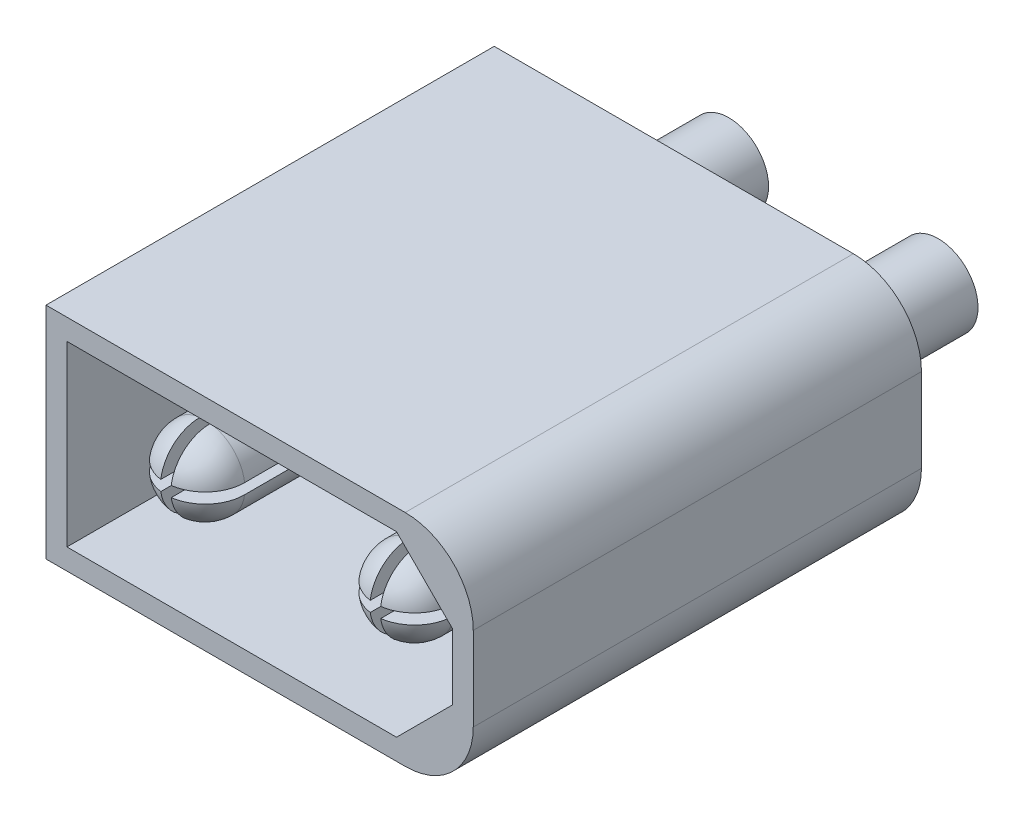
SolidWorks part; units mm, degrees
ref_plane "Front Plane" through (0, 0, 0) normal (0, 0, 1) x (1, 0, 0)
ref_plane "Top Plane" through (0, 0, 0) normal (0, 1, 0) x (1, 0, 0)
ref_plane "Right Plane" through (0, 0, 0) normal (1, 0, 0) x (0, 0, -1)
sketch "Sketch1" plane through (0, 0, 0) normal (0, 0, 1) x (1, 0, 0)
  line L0 (0, 0) -> (10.2, 0) construction
  line L1 (0, -2.625) -> (0, 2.625)
  line L2 (0, 2.625) -> (8.575, 2.625)
  line L4 (10.2, 1) -> (10.2, -1)
  line L5 (5.1, 0) -> (5.1, 1.3562) construction
  line L7 (0, -2.625) -> (8.575, -2.625)
  line L8 (0.5, 2.125) -> (8.3679, 2.125)
  line L9 (8.3679, 2.125) -> (9.7, 0.7929)
  line L10 (9.7, 0.7929) -> (9.7, -0.7929)
  line L11 (8.3679, -2.125) -> (9.7, -0.7929)
  line L12 (0.5, -2.125) -> (8.3679, -2.125)
  line L13 (0.5, -2.125) -> (0.5, 2.125)
  line L14 (8.575, 2.625) -> (10.2, 1) construction
  line L15 (8.575, -2.625) -> (10.2, -1) construction
  circle A0 centre (2.6, 0) radius 0.95
  circle A2 centre (7.6, 0) radius 0.95
  arc A3 (8.575, 2.625) -> (10.2, 1) centre (8.575, 1) cw
  arc A4 (8.575, -2.625) -> (10.2, -1) centre (8.575, -1) ccw
  dimension "D6" = 1.9
  dimension "D1" = 5.25
  dimension "D2" = 10.2
  dimension "D3" = 135
  dimension "D4" = 2.5
  dimension "D7" = 2
  dimension "D5" = 0.5
extrude "Boss-Extrude1" add sketch "Sketch1" along normal blind 10.7 contours L1 L7 A4 L4 A3 L2 L12 L13 L8 L9 L10 L11 region at (0.1147, 0, 0)
extrude "Boss-Extrude5" add sketch "Sketch1<4>" along normal blind 9.5 and the other way blind 3 separate body contours A0 | A2 region at (2.6, 0, 0)
sketch "Sketch1<4>" plane through (0, 0, 0) normal (0, 0, 1) x (1, 0, 0) same geometry as "Sketch1"
ref_plane "Plane1" through (0, 0, 1) normal (0, 0, -1) x (-1, 0, 0)
sketch "Sketch3" plane through (0, 0, 1) normal (0, 0, -1) x (-1, 0, 0)
  line L0 (-0.5, -2.125) -> (-0.5, 2.125) construction
  line L1 (-0.5, -2.125) -> (-8.3679, -2.125) construction
  line L2 (-8.3679, -2.125) -> (-9.7, -0.7929) construction
  line L3 (-9.7, 0.7929) -> (-9.7, -0.7929) construction
  line L4 (-8.3679, 2.125) -> (-9.7, 0.7929) construction
  line L5 (-0.5, 2.125) -> (-8.3679, 2.125) construction
  line L6 (-0.5, -2.125) -> (-0.5, 2.125)
  line L7 (-0.5, -2.125) -> (-8.3679, -2.125)
  line L8 (-8.3679, -2.125) -> (-9.7, -0.7929)
  line L9 (-9.7, 0.7929) -> (-9.7, -0.7929)
  line L10 (-8.3679, 2.125) -> (-9.7, 0.7929)
  line L11 (-0.5, 2.125) -> (-8.3679, 2.125)
extrude "Boss-Extrude3" add sketch "Sketch3" against normal blind 2.5
dome "Dome1" faces to dome 1 distance 0.95 reverse direction no elliptical dome no face at (6.65, 0, 9.5) parameters "D1"=0.95
dome "Dome2" faces to dome 1 distance 0.95 reverse direction no elliptical dome no face at (3.55, 0, 9.5) parameters "D1"=0.95
ref_plane "Plane2" through (0, 0, 6) normal (0, 0, 1) x (1, 0, 0)
sketch "Sketch4" plane through (0, 0, 6) normal (0, 0, 1) x (1, 0, 0)
  line L0 (7.6, 0) -> (2.6, 0) construction
  line L1 (5.1, 0) -> (5.1, -4.8964) construction
  line L2 (7.6, 0) -> (7.6, 0.95) construction
  line L3 (7.475, 0.9417) -> (7.475, 0.125)
  line L4 (7.725, 0.9417) -> (7.725, 0.125)
  line L5 (8.5417, -0.125) -> (7.725, -0.125)
  line L6 (8.5417, 0.125) -> (7.725, 0.125)
  line L7 (7.475, -0.9417) -> (7.475, -0.125)
  line L8 (7.725, -0.9417) -> (7.725, -0.125)
  line L9 (6.6583, 0.125) -> (7.475, 0.125)
  line L10 (6.6583, -0.125) -> (7.475, -0.125)
  line L11 (2.6, 0) -> (2.6, 0.95) construction
  line L12 (3.5417, -0.125) -> (2.725, -0.125)
  line L13 (3.5417, 0.125) -> (2.725, 0.125)
  line L14 (2.475, -0.9417) -> (2.475, -0.125)
  line L15 (2.725, -0.9417) -> (2.725, -0.125)
  line L16 (1.6583, 0.125) -> (2.475, 0.125)
  line L17 (1.6583, -0.125) -> (2.475, -0.125)
  line L18 (2.475, 0.9417) -> (2.475, 0.125)
  line L19 (2.725, 0.9417) -> (2.725, 0.125)
  circle A0 centre (7.6, 0) radius 0.95 construction
  circle A1 centre (2.6, 0) radius 0.95 construction
  arc A2 (7.725, 0.9417) -> (7.475, 0.9417) centre (7.6, 0) ccw
  circle A3 centre (2.6, 0) radius 0.95 construction
  arc A4 (8.5417, -0.125) -> (8.5417, 0.125) centre (7.6, 0) ccw
  arc A5 (7.475, -0.9417) -> (7.725, -0.9417) centre (7.6, 0) ccw
  arc A6 (6.6583, 0.125) -> (6.6583, -0.125) centre (7.6, 0) ccw
  arc A7 (3.5417, 0.125) -> (3.5417, -0.125) centre (2.6, 0) cw
  arc A8 (2.725, -0.9417) -> (2.475, -0.9417) centre (2.6, 0) cw
  arc A9 (1.6583, -0.125) -> (1.6583, 0.125) centre (2.6, 0) cw
  arc A10 (2.475, 0.9417) -> (2.725, 0.9417) centre (2.6, 0) cw
  point P28 (7.6, 0)
  dimension "D1" = 0.25
  dimension "D2" = 4
extrude "Cut-Extrude1" cut sketch "Sketch4" along normal through all
